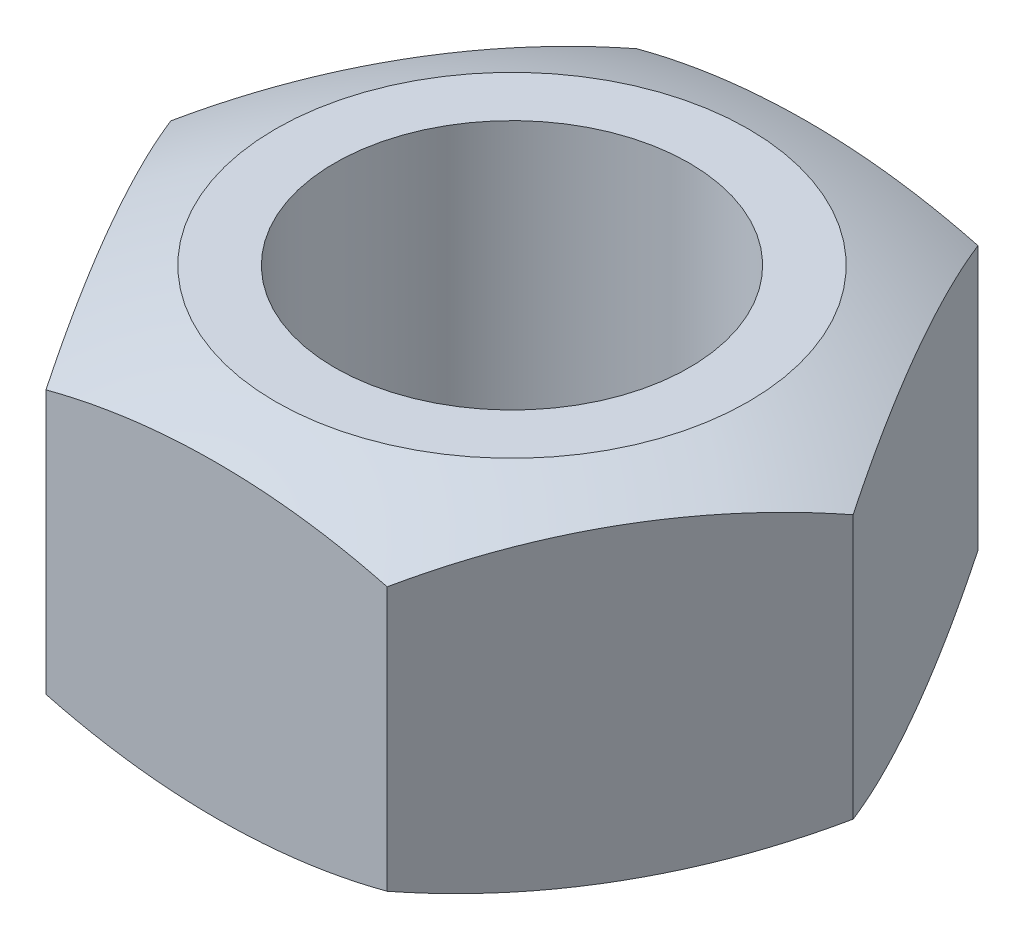
SolidWorks part; units mm, degrees
ref_plane "Front" through (0, 0, 0) normal (0, 0, 1) x (1, 0, 0)
ref_plane "Top" through (0, 0, 0) normal (0, 1, 0) x (1, 0, 0)
ref_plane "Right" through (0, 0, 0) normal (1, 0, 0) x (0, 0, -1)
sketch "profile" plane through (0, 0, 0) normal (0, 1, 0) x (1, 0, 0)
  line L1 (5.7735, 0) -> (2.8868, 5)
  line L2 (2.8868, 5) -> (-2.8868, 5)
  line L3 (-2.8868, 5) -> (-5.7735, 0)
  line L4 (-5.7735, 0) -> (-2.8868, -5)
  line L5 (-2.8868, -5) -> (2.8868, -5)
  line L6 (2.8868, -5) -> (5.7735, 0)
  circle A0 centre (0, 0) radius 5 construction
  dimension "width" = 10
extrude "body" add sketch "profile" along normal blind 6
sketch "thread"
  circle A0 centre (0, 0) radius 3
  dimension "diameter" = 6
revolve "fillet" cut sketch "Sketch7"
sketch "Sketch7" plane through (0, 0, 0) normal (0, 0, 1) x (1, 0, 0)
  line L0 (0, 0) -> (0, 5.3875) construction
  line L3 (5.7735, 6) -> (5.7735, 0) construction
  line L4 (2.8868, 0) -> (5.7735, 0) construction
  line L5 (4, 0.8307) -> (4, -1.2581) construction
  line L6 (-0.3098, 3) -> (0.7587, 3) construction
  line L7 (-2.8868, 0) -> (2.8868, 0) construction
  line L8 (-2.8868, 6) -> (2.8868, 6) construction
  line L9 (5.7735, 5.2312) -> (5.7735, 0.7688)
  line L10 (0, 6.6672) -> (0, 7.5046)
  line L11 (0, 7.5046) -> (6.273, 7.5046)
  line L12 (6.273, 7.5046) -> (6.273, -3.4922)
  line L13 (6.273, -3.4922) -> (0, -3.4922)
  line L14 (0, -3.4922) -> (0, -0.6672)
  arc A0 (0, -0.6672) -> (5.7735, 0.7688) centre (0, 11.6575) ccw
  arc A1 (0, 6.6672) -> (5.7735, 5.2312) centre (0, -5.6575) cw
  point P12 (4, 0)
  dimension "D1" = 360
  dimension "halfwidth" = 4
extrude "hole" cut sketch "thread" against normal through all
